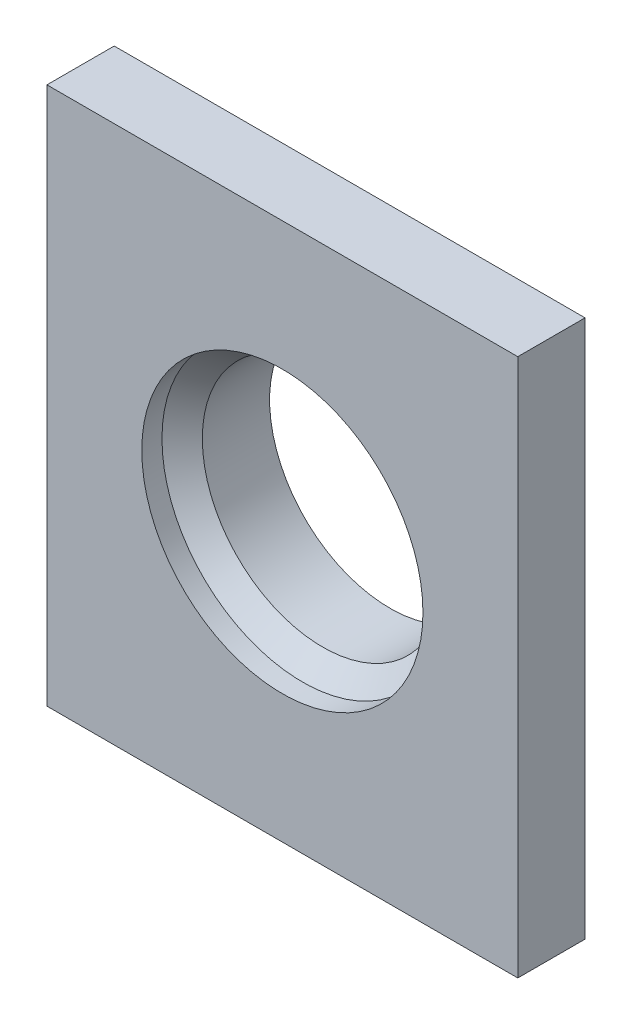
SolidWorks part; units mm, degrees
ref_plane "Front Plane" through (0, 0, 0) normal (0, 0, 1) x (1, 0, 0)
ref_plane "Top Plane" through (0, 0, 0) normal (0, 1, 0) x (1, 0, 0)
ref_plane "Right Plane" through (0, 0, 0) normal (1, 0, 0) x (0, 0, -1)
sketch "Sketch4" plane through (0, 0, 0) normal (0, 0, 1) x (1, 0, 0)
  circle A0 centre (0, 0) radius 8.7 construction
  dimension "D1" = 17.4
sketch "Sketch1" plane through (0, 0, 0) normal (0, 0, 1) x (1, 0, 0)
  line L1 (-17.5, 20) -> (17.5, 20)
  line L2 (-17.5, 20) -> (-17.5, -20)
  line L3 (-17.5, -20) -> (17.5, -20)
  line L4 (17.5, 20) -> (17.5, -20)
  line L5 (-17.5, 20) -> (17.5, -20) construction
  line L6 (-17.5, -20) -> (17.5, 20) construction
  point P0 (0, 0)
  dimension "D1" = 40
  dimension "D2" = 35
extrude "Boss-Extrude1" add sketch "Sketch1" along normal mid plane 5
sketch "Sketch5" plane through (0, 0, -2.5) normal (0, 0, -1) x (-1, 0, 0)
  circle A3 centre (0, 0) radius 10.95
  circle A4 centre (0, 0) radius 10.95
  dimension "D1" = 2.25
extrude "Boss-Extrude2" add sketch "Sketch5" along normal blind 3
sketch "Sketch2" plane through (0, 0, 2.5) normal (0, 0, 1) x (1, 0, 0)
  circle A3 centre (0, 0) radius 8.95
  circle A4 centre (0, 0) radius 8.95
  dimension "D1" = 0.25
extrude "Cut-Extrude1" cut sketch "Sketch2" against normal through all
sketch "Sketch6" plane through (0, 0, 2.5) normal (0, 0, 1) x (1, 0, 0)
  circle A1 centre (0, 0) radius 10.95 construction
  circle A2 centre (0, 0) radius 10.45
  point P1 (0, 0)
  point P5 (0, 0)
  dimension "D1" = 0.5
extrude "Cut-Extrude2" cut sketch "Sketch6" against normal offset from surface (3 mm away) 5 up to face at (8.95, 0, -5.5)
chamfer "Chamfer2" distance 1.5 angle 45 2 edges at (-10.45, 0, -0.5) (-10.95, 0, -2.5)
